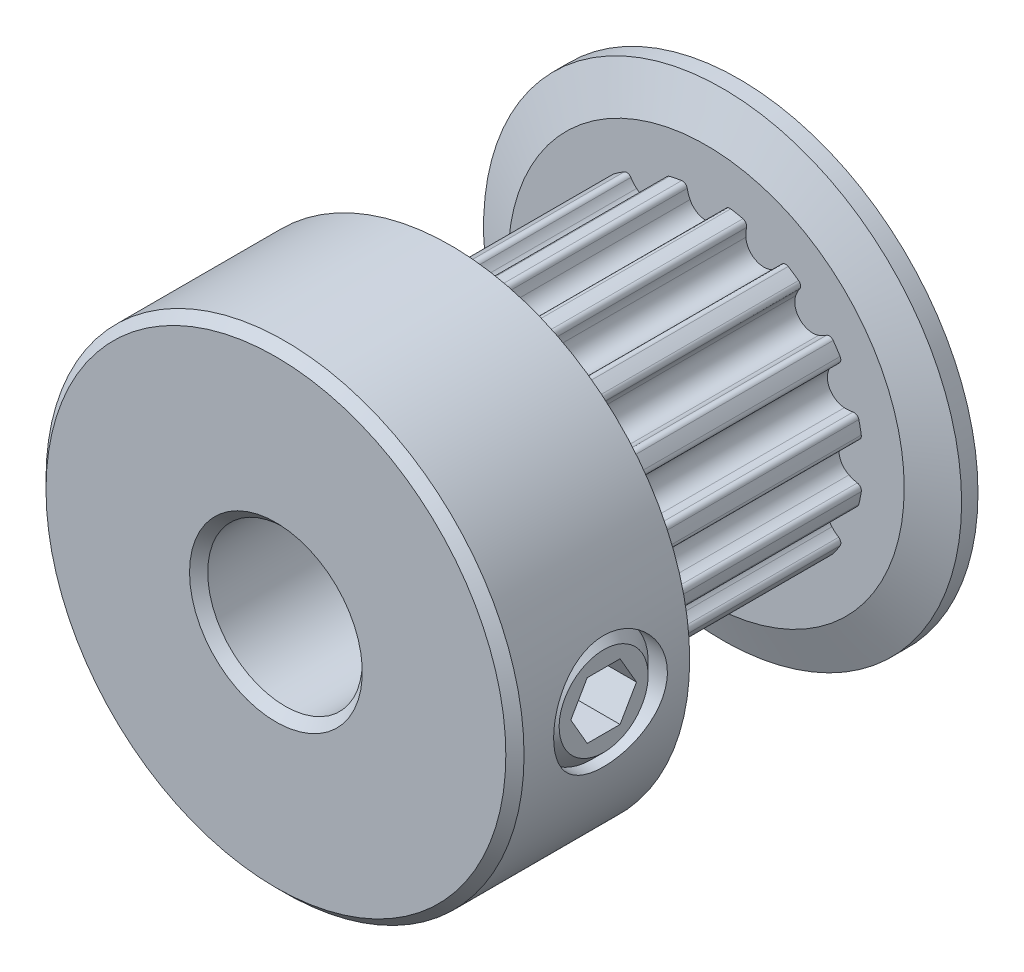
SolidWorks part; units mm, degrees
ref_plane "Front Plane" through (0, 0, 0) normal (0, 0, 1) x (1, 0, 0)
ref_plane "Top Plane" through (0, 0, 0) normal (0, 1, 0) x (1, 0, 0)
ref_plane "Right Plane" through (0, 0, 0) normal (1, 0, 0) x (0, 0, -1)
sketch "Sketch1" plane through (0, 0, 0) normal (0, 0, 1) x (1, 0, 0)
  line L1 (-1.706, 4.0885) -> (1.706, 4.0885) construction
  line L4 (0, 0) -> (0, 4.0885) construction
  line L5 (0, 4.0885) -> (0, 10.3644) construction
  line L6 (0, 5.0925) -> (1.9611, 4.6998) construction
  line L7 (1.9611, 4.6998) -> (2.5723, 4.4447) construction
  line L8 (1.9611, 4.6998) -> (1.706, 4.0885) construction
  line L9 (-1.9611, 4.6998) -> (-1.706, 4.0885) construction
  line L10 (-1.8632, 4.4654) -> (-3.0736, 7.366)
  line L11 (-3.0736, 7.366) -> (3.0736, 7.366)
  line L12 (3.0736, 7.366) -> (1.8632, 4.4654)
  circle A0 centre (0, 0) radius 5.0925 construction
  circle A1 centre (0, 0) radius 7.366 construction
  circle A2 centre (0, 0) radius 4.8385 construction
  arc A3 (-0.4989, 4.4003) -> (0.4989, 4.4003) centre (0, 4.6435) ccw
  arc A4 (-0.4989, 4.4003) -> (-0.5836, 4.6582) centre (0.4, 4.8385) cw
  arc A5 (-1.8632, 4.4654) -> (-0.7545, 4.7793) centre (0, 0) cw
  arc A6 (-0.5836, 4.6582) -> (-0.7545, 4.7793) centre (-0.7312, 4.6311) ccw
  arc A7 (1.8632, 4.4654) -> (0.7545, 4.7793) centre (0, 0) ccw
  arc A8 (0.5836, 4.6582) -> (0.7545, 4.7793) centre (0.7312, 4.6311) cw
  arc A9 (0.4989, 4.4003) -> (0.5836, 4.6582) centre (-0.4, 4.8385) ccw
  point P6 (0, 20.9083)
  point P11 (0, 5.0925)
  point P13 (0, 7.366)
  point P14 (0, 4.8385)
  dimension "D1" = 10.5439
  dimension "D2" = 5.2719
sketch "Sketch2" plane through (0, 0, 0) normal (1, 0, 0) x (0, 0, -1)
  line L0 (-7.135, 2.3812) -> (7.135, 2.3812)
  line L1 (-7.135, 2.3812) -> (-7.135, 7.366)
  line L2 (-1.75, 7.366) -> (-7.135, 7.366)
  line L3 (-2.255, 2.3813) -> (-2.255, 7.366) construction
  line L4 (-2.255, 7.366) -> (-1.245, 7.366) construction
  line L5 (-1.245, 7.366) -> (-1.245, 4.8385) construction
  line L6 (-1.245, 4.8385) -> (6.125, 4.8385)
  line L7 (6.125, 4.8385) -> (6.125, 7.366) construction
  line L8 (6.125, 7.366) -> (7.135, 7.366) construction
  line L9 (7.135, 7.366) -> (7.135, 2.3812)
  line L10 (-7.135, 0) -> (7.135, 0) construction
  line L11 (6.63, 7.366) -> (6.125, 6.1022)
  line L12 (-1.245, 6.1022) -> (-1.75, 7.366)
  line L14 (-1.245, 6.1022) -> (-1.245, 4.8385)
  line L15 (6.125, 4.8385) -> (6.125, 6.1022)
  line L16 (6.63, 7.366) -> (7.135, 7.366)
  arc A0 (-1.245, 6.1022) -> (-1.75, 7.366) centre (-3.0788, 6.1022) ccw construction
  arc A1 (6.125, 6.1022) -> (6.63, 7.366) centre (7.9588, 6.1022) cw construction
  point P12 (-1.245, 6.1022)
  point P14 (-1.75, 7.366)
  point P20 (6.125, 6.1022)
  point P21 (6.63, 7.366)
  point P25 (6.125, 0)
  point P26 (-1.245, 0)
  dimension "OA" = 14.27
  dimension "Bore" = 4.7625
  dimension "Outside Width" = 8.38
  dimension "Inside Width" = 7.37
revolve "Revolve1" add sketch "Sketch2" angle 360 mid plane about L10
sketch "Sketch3" plane through (0, 0, 0) normal (0, 0, 1) x (1, 0, 0)
  line L6 (3.0736, 7.366) -> (-3.0736, 7.366)
  line L7 (1.8632, 4.4654) -> (3.0736, 7.366)
  line L8 (-3.0736, 7.366) -> (-1.8632, 4.4654)
  line L9 (3.0736, 7.366) -> (-3.0736, 7.366)
  line L10 (1.8632, 4.4654) -> (3.0736, 7.366)
  line L11 (-3.0736, 7.366) -> (-1.8632, 4.4654)
  arc A8 (1.8632, 4.4654) -> (0.7545, 4.7793) centre (0, 0) ccw
  arc A9 (0.7545, 4.7793) -> (0.5836, 4.6582) centre (0.7312, 4.6311) ccw
  arc A10 (0.4989, 4.4003) -> (0.5836, 4.6582) centre (-0.4, 4.8385) ccw
  arc A11 (-0.4989, 4.4003) -> (0.4989, 4.4003) centre (0, 4.6435) ccw
  arc A12 (-0.5836, 4.6582) -> (-0.4989, 4.4003) centre (0.4, 4.8385) ccw
  arc A13 (-0.5836, 4.6582) -> (-0.7545, 4.7793) centre (-0.7312, 4.6311) ccw
  arc A14 (-0.7545, 4.7793) -> (-1.8632, 4.4654) centre (0, 0) ccw
  arc A15 (1.8632, 4.4654) -> (0.7545, 4.7793) centre (0, 0) ccw
  arc A16 (0.7545, 4.7793) -> (0.5836, 4.6582) centre (0.7312, 4.6311) ccw
  arc A17 (0.4989, 4.4003) -> (0.5836, 4.6582) centre (-0.4, 4.8385) ccw
  arc A18 (-0.4989, 4.4003) -> (0.4989, 4.4003) centre (0, 4.6435) ccw
  arc A19 (-0.5836, 4.6582) -> (-0.4989, 4.4003) centre (0.4, 4.8385) ccw
  arc A20 (-0.5836, 4.6582) -> (-0.7545, 4.7793) centre (-0.7312, 4.6311) ccw
  arc A21 (-0.7545, 4.7793) -> (-1.8632, 4.4654) centre (0, 0) ccw
  dimension "D1" = 0
extrude "Cut-Extrude1" cut sketch "Sketch3" against normal up to vertex (6.125 mm away) from vertex up to point (0, 4.8385, -6.125) starting at point (0, 4.8385, 1.245)
pattern_circular "CirPattern1" count 16 over 360 about axis through (0, 0, 7.135) along (0, 0, 1) of "Cut-Extrude1"
sketch "Sketch4" plane through (0, 0, 0) normal (1, 0, 0) x (0, -1, 0)
  line L0 (0, -1.245) -> (0, -7.135) construction
  line L1 (-2.3812, -7.135) -> (2.3812, -7.135) construction
  line L2 (6.1022, -1.245) -> (-6.1022, -1.245) construction
  circle A0 centre (0, -4.19) radius 1.7526
extrude "Cut-Extrude2" cut sketch "Sketch4" along normal through all
ref_plane "Plane1" through (0, 0, 4.19) normal (0, 0, 1) x (1, 0, 0)
sketch "Sketch5" plane through (0, 0, 4.19) normal (0, 0, 1) x (1, 0, 0)
  line L0 (0, 0) -> (0, 7.366) construction
  line L1 (2.3812, -1.3716) -> (2.3812, 0)
  line L2 (2.7622, -1.7526) -> (6.7735, -1.7526)
  line L3 (2.3812, 0) -> (7.366, 0) construction
  line L4 (2.3812, 0) -> (7.1545, 0)
  line L5 (7.1545, 0) -> (7.1545, -1.3716)
  line L6 (2.7622, -1.7526) -> (2.3812, -1.3716)
  line L7 (7.1545, -1.3716) -> (6.7735, -1.7526)
  circle A0 centre (0, 0) radius 7.366 construction
  circle A1 centre (0, 0) radius 2.3812 construction
  point P2 (2.3812, -1.7526)
  point P11 (7.1545, -1.7526)
revolve "Revolve2" add sketch "Sketch5" angle 360 mid plane about L4
sketch "Sketch6" plane through (7.1545, 5.3841, 0) normal (-1, 0, 0) x (0, -1, 0)
  line L1 (5.3841, 5.2019) -> (4.5078, 4.6959)
  line L2 (4.5078, 4.6959) -> (4.5078, 3.6841)
  line L3 (4.5078, 3.6841) -> (5.3841, 3.1781)
  line L4 (5.3841, 3.1781) -> (6.2604, 3.6841)
  line L5 (6.2604, 3.6841) -> (6.2604, 4.6959)
  line L6 (6.2604, 4.6959) -> (5.3841, 5.2019)
  circle A0 centre (5.3841, 4.19) radius 0.8763 construction
  dimension "D1" = 1.7526
extrude "Cut-Extrude3" cut sketch "Sketch6" along normal blind 1.3144
chamfer "Chamfer1" distance 0.2807 angle 45 2 edges at (2.3812, 0, 7.135) (7.366, 0, 7.135)
ref_axis "Center Axis 1" through (0, 0, -7.135) along (0, 0, 1)
ref_plane "Contact Plane 1" through (0, 0, 7.135) normal (0, 0, 1) x (1, 0, 0)
ref_plane "Contact Plane 2" through (0, 0, -7.135) normal (0, 0, -1) x (-1, 0, 0)
equation "\"D2@Sketch1\"= \"D1@Sketch1\" / 2"
equation "\"D1@Sketch6\" = \"Set Screw@Sketch4\" / 2"
equation "\"D1@Cut-Extrude3\" = \"D1@Sketch6\"*.75"
